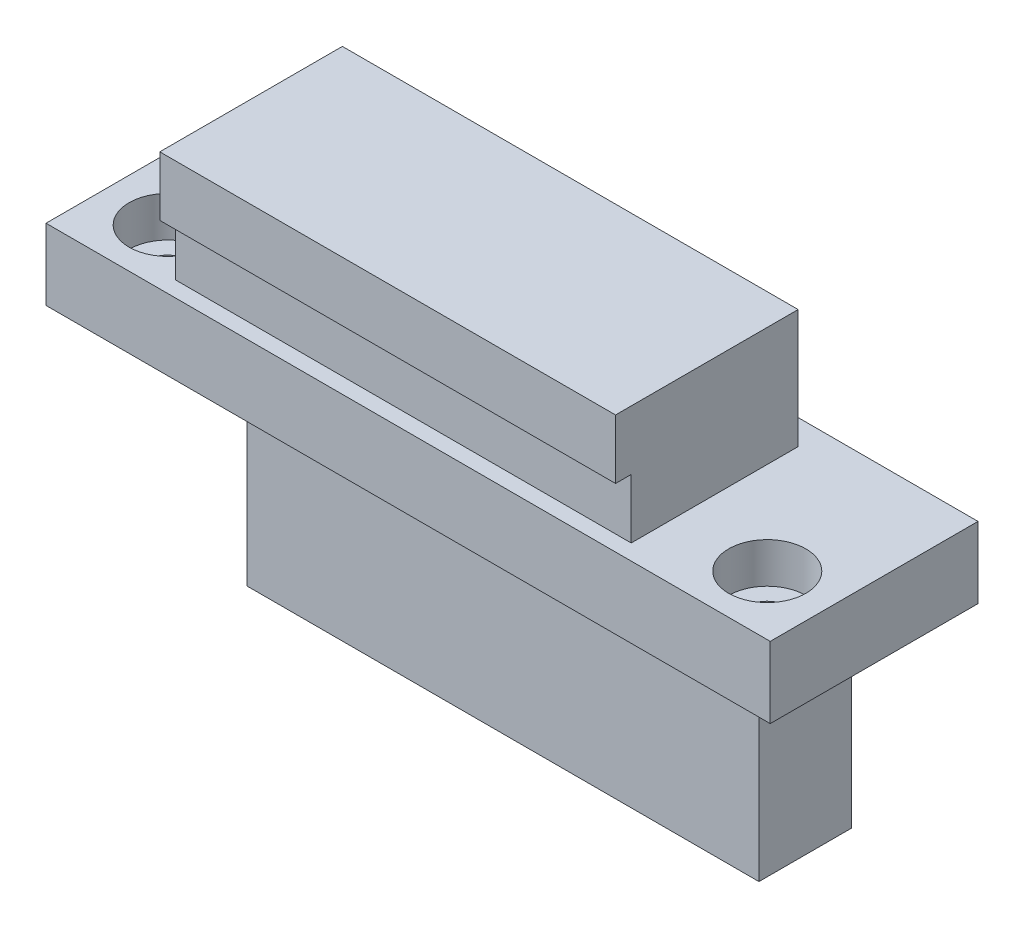
SolidWorks part; units mm, degrees
ref_plane "Přední" through (0, 0, 0) normal (0, 0, 1) x (1, 0, 0)
ref_plane "Horní" through (0, 0, 0) normal (0, 1, 0) x (1, 0, 0)
ref_plane "Pravá" through (0, 0, 0) normal (1, 0, 0) x (0, 0, -1)
sketch "Skica1" plane through (0, 0, 0) normal (0, 1, 0) x (1, 0, 0)
  line L1 (30.5, 8.75) -> (-30.5, 8.75)
  line L2 (30.5, 8.75) -> (30.5, -8.75)
  line L3 (30.5, -8.75) -> (-30.5, -8.75)
  line L4 (-30.5, 8.75) -> (-30.5, -8.75)
  line L5 (30.5, 8.75) -> (-30.5, -8.75) construction
  line L6 (30.5, -8.75) -> (-30.5, 8.75) construction
  point P0 (0, 0)
  dimension "D1" = 61
  dimension "D2" = 17.5
extrude "Přidat vysunutím1" add sketch "Skica1" along normal blind 6
sketch "Skica2" plane through (0, 0, 0) normal (0, -1, 0) x (1, 0, 0)
  line L0 (0, 8.75) -> (0, -7.05) construction
  line L1 (21.55, -7.05) -> (-21.55, -7.05)
  line L2 (21.55, -7.05) -> (21.55, 0.75)
  line L3 (21.55, 0.75) -> (-21.55, 0.75)
  line L4 (-21.55, -7.05) -> (-21.55, 0.75)
  line L5 (-30.5, 8.75) -> (30.5, 8.75) construction
  line L6 (30.5, -8.75) -> (-30.5, -8.75) construction
  dimension "D1" = 7.8
  dimension "D2" = 43.1
  dimension "D3" = 1.7
extrude "Přidat vysunutím2" add sketch "Skica2" along normal blind 20
hole_wizard "Válcové zahloubení pro M3 šrouby s vnitřním šestihranem1" positions "Skica4" profile "Skica3" counterbore size "M3" standard "ISO"
sketch "Skica4" plane through (0, 6, 0) normal (0, 1, 0) x (1, 0, 0)
  line L0 (-25.25, -3.75) -> (25.25, -3.75) construction
  line L3 (0, -8.75) -> (0, -3.75) construction
  line L4 (-30.5, -8.75) -> (30.5, -8.75) construction
  point P0 (-25.25, -3.75)
  point P2 (25.25, -3.75)
  dimension "D1" = 5
  dimension "D2" = 50.5
sketch "Skica3" plane through (-25.25, 6, 3.75) normal (1, 0, 0) x (0, 0, 1)
  line L0 (0, 0) -> (0, 11.0215)
  line L1 (0, 11.0215) -> (1.7, 10)
  line L2 (1.7, 10) -> (1.7, 3.4)
  line L3 (1.7, 3.4) -> (3.25, 3.4)
  line L4 (3.25, 3.4) -> (3.25, 0)
  line L5 (3.25, 0) -> (0, 0)
  line L10 (0, 11.0215) -> (-1.7, 10) construction
  line L11 (0, -6.35) -> (0, 107.95) construction
  dimension "Průměr díry" = 3.4
  dimension "Hloubka díry" = 10
  dimension "Průměr válcového zahloubení" = 6.5
  dimension "Hloubka válcového zahloubení" = 3.4
  dimension "Úhel vrtání" = 118
sketch "Skica5" plane through (0, 6, 0) normal (0, 1, 0) x (1, 0, 0)
  line L1 (-20.9162, -7.4309) -> (17.4714, -7.4309)
  line L2 (-20.9162, -7.4309) -> (-20.9162, 6.6297)
  line L3 (-20.9162, 6.6297) -> (17.4714, 6.6297)
  line L4 (17.4714, -7.4309) -> (17.4714, 6.6297)
extrude "Přidat vysunutím3" add sketch "Skica5" along normal blind 10
sketch "Skica6" plane through (0, 0, 7.4309) normal (0, 0, 1) x (1, 0, 0)
  line L0 (17.4714, 16) -> (17.4714, 6) construction
  line L1 (-20.9162, 16) -> (17.4714, 16)
  line L2 (-20.9162, 16) -> (-20.9162, 11)
  line L3 (-20.9162, 11) -> (17.4714, 11)
  line L4 (17.4714, 16) -> (17.4714, 11)
extrude "Přidat vysunutím4" add sketch "Skica6" along normal up to surface (1.3191 mm away) up to face at (0, 3, 8.75)
